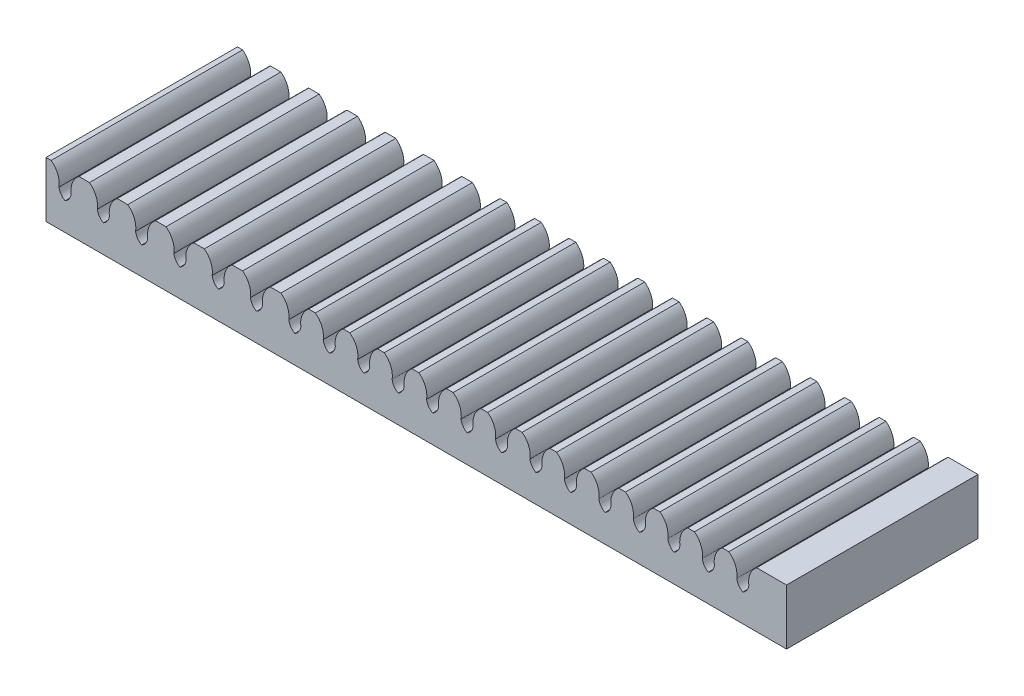
SolidWorks part; units mm, degrees
ref_plane "Front Plane" through (0, 0, 0) normal (0, 0, 1) x (1, 0, 0)
ref_plane "Top Plane" through (0, 0, 0) normal (0, 1, 0) x (1, 0, 0)
ref_plane "Right Plane" through (0, 0, 0) normal (1, 0, 0) x (0, 0, -1)
sketch "Sketch1" plane through (0, 0, 0) normal (0, 0, 1) x (1, 0, 0)
  line L0 (28, 7) -> (-39.3732, 7)
  line L1 (-39.3732, 7) -> (-39.3732, -0.2491)
  line L2 (-39.3732, -0.2491) -> (0.9392, -0.2491)
  line L3 (0.9392, -0.2491) -> (57.3333, -0.2491)
  line L4 (57.3333, -0.2491) -> (57.3333, 7)
  line L5 (57.3333, 7) -> (28, 7)
  point P0 (57.3333, 3.3754)
  dimension "D1" = 96.7065
extrude "Boss-Extrude1" add sketch "Sketch1" along normal blind 25
sketch "Sketch2" plane through (0, 0, 0) normal (0, 0, 1) x (1, 0, 0)
  line L0 (-6.8813, 0.8955) -> (-6.8813, 9.6802) construction
  arc A5 (-6.8813, 3.3484) -> (-7.6713, 4.4984) centre (-6.1725, 4.6817) cw
  arc A12 (-7.6713, 4.4984) -> (-8.9813, 7.188) centre (-10.3038, 4.8801) ccw
  arc A13 (-6.0913, 4.4984) -> (-4.7813, 7.188) centre (-3.4588, 4.8801) cw
  arc A14 (-6.8813, 3.3484) -> (-6.0913, 4.4984) centre (-7.5901, 4.6817) ccw
  arc A15 (-8.9813, 7.188) -> (-4.7813, 7.188) centre (-6.8813, 3.6353) cw
  dimension "D4" = 2.66
  dimension "D5" = 1.51
  dimension "D6" = 1.15
  dimension "D8" = 2.1
  dimension "D10" = 0.79
extrude "Cut-Extrude1" cut sketch "Sketch2" along normal blind 26.12
pattern_linear "LPattern1" count 10 spacing 5 along (-1, 0, 0) count 14 spacing 4.5 along (1, 0, 0) of "Cut-Extrude1" pattern seed only yes
